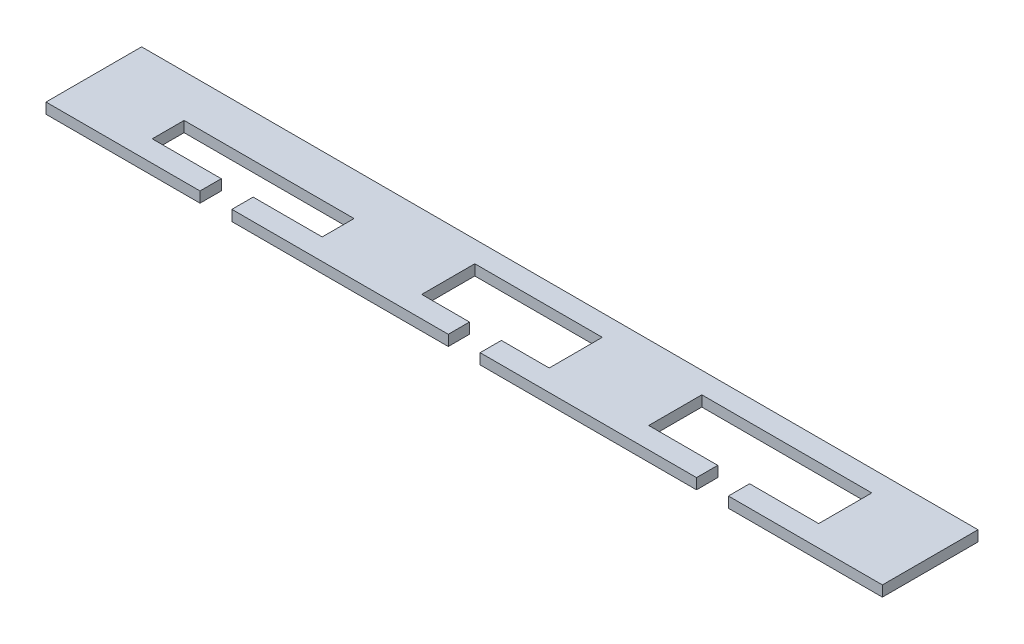
SolidWorks part; units mm, degrees
ref_plane "Front Plane" through (0, 0, 0) normal (0, 0, 1) x (1, 0, 0)
ref_plane "Top Plane" through (0, 0, 0) normal (0, 1, 0) x (1, 0, 0)
ref_plane "Right Plane" through (0, 0, 0) normal (1, 0, 0) x (0, 0, -1)
sketch "Sketch1" plane through (0, 0, 0) normal (0, 1, 0) x (1, 0, 0)
  line L0 (0, 57.15) -> (1000.0005, 57.15) construction
  line L2 (0, 0) -> (0, 114.3)
  line L3 (0, 114.3) -> (1000.0005, 114.3)
  line L4 (1000.0005, 0) -> (1000.0005, 114.3)
  line L9 (101.6, 25.4) -> (184.15, 25.4)
  line L10 (101.6, 25.4) -> (101.6, 63.5)
  line L12 (304.8, 25.4) -> (304.8, 63.5)
  line L17 (0, -31.5189) -> (406.4, -31.5189) construction
  line L18 (0, -31.5189) -> (0, -107.7189) construction
  line L19 (0, -107.7189) -> (406.4, -107.7189) construction
  line L20 (406.4, -31.5189) -> (406.4, -107.7189) construction
  line L21 (593.6005, -31.5189) -> (1000.0005, -31.5189) construction
  line L22 (593.6005, -31.5189) -> (593.6005, -107.7189) construction
  line L23 (593.6005, -107.7189) -> (1000.0005, -107.7189) construction
  line L24 (1000.0005, -31.5189) -> (1000.0005, -107.7189) construction
  line L25 (203.2, -31.5189) -> (203.2, -107.7189) construction
  line L26 (796.8005, -107.7189) -> (796.8005, -31.5189) construction
  line L27 (203.2, -31.5189) -> (203.2, 114.3) construction
  line L28 (796.8005, -31.5189) -> (796.8005, 114.3) construction
  line L29 (500.0003, -101.6) -> (500.0003, 114.3) construction
  line L30 (0, 0) -> (184.15, 0)
  line L35 (101.6, 63.5) -> (304.8, 63.5)
  line L36 (423.8003, 88.9) -> (576.2003, 88.9)
  line L37 (423.8003, 88.9) -> (423.8003, 25.4)
  line L38 (423.8003, 25.4) -> (480.9503, 25.4)
  line L39 (576.2003, 88.9) -> (576.2003, 25.4)
  line L40 (423.8003, 88.9) -> (576.2003, 25.4) construction
  line L41 (423.8003, 25.4) -> (576.2003, 88.9) construction
  line L43 (898.4005, 25.4) -> (815.8505, 25.4)
  line L44 (898.4005, 25.4) -> (898.4005, 88.9)
  line L46 (550.8003, 0) -> (777.7505, 0)
  line L48 (203.2, 12.7813) -> (184.15, 12.7813) construction
  line L49 (203.2, 12.7813) -> (222.25, 12.7813) construction
  line L50 (184.15, 25.4) -> (184.15, 0)
  line L51 (222.25, 25.4) -> (222.25, 0)
  line L52 (222.25, 25.4) -> (304.8, 25.4)
  line L53 (222.25, 0) -> (449.2003, 0)
  line L54 (796.8005, 12.7813) -> (777.7505, 12.7813) construction
  line L55 (796.8005, 12.7813) -> (815.8505, 12.7813) construction
  line L56 (777.7505, 25.4) -> (777.7505, 0)
  line L57 (815.8505, 25.4) -> (815.8505, 0)
  line L58 (815.8505, 0) -> (1000.0005, 0)
  line L59 (777.7505, 25.4) -> (695.2005, 25.4)
  line L60 (480.9503, 12.7813) -> (519.0503, 12.7813) construction
  line L61 (480.9503, 25.4) -> (480.9503, 0)
  line L62 (480.9503, 0) -> (449.2003, 0)
  line L63 (519.0503, 25.4) -> (519.0503, 0)
  line L64 (519.0503, 0) -> (550.8003, 0)
  line L65 (519.0503, 25.4) -> (576.2003, 25.4)
  line L66 (898.4005, 88.9) -> (695.2005, 88.9)
  line L67 (695.2005, 88.9) -> (695.2005, 25.4)
  point P36 (500.0003, 57.15)
  point P57 (500.0003, 12.7813)
  dimension "D1" = 406.4
  dimension "D2" = 76.2
  dimension "D3" = 1000.0005
  dimension "D4" = 63.5
  dimension "D5" = 38.1
  dimension "D6" = 203.2
  dimension "D7" = 38.1
  dimension "D8" = 19.05
  dimension "D9" = 19.05
  dimension "D10" = 152.4
  dimension "D11" = 63.5
  dimension "D12" = 25.4
  dimension "D13" = 25.4
  dimension "D14" = 184.15
  dimension "D15" = 101.6
  dimension "D16" = 38.1
extrude "Boss-Extrude1" add sketch "Sketch1" along normal blind 12.7
